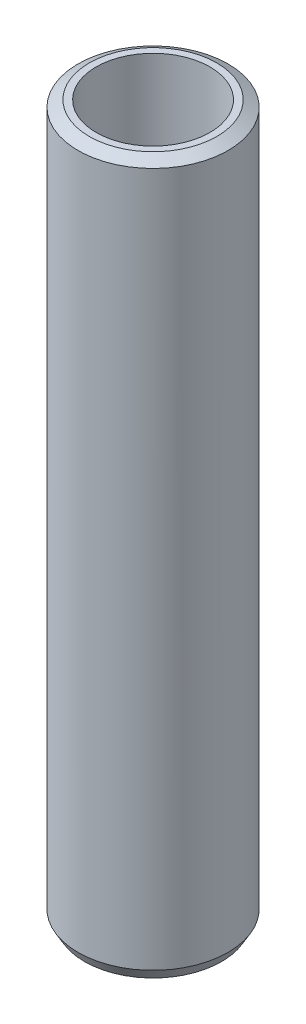
SolidWorks part; units mm, degrees
ref_plane "Front Plane" through (0, 0, 0) normal (0, 0, 1) x (1, 0, 0)
ref_plane "Top Plane" through (0, 0, 0) normal (0, 1, 0) x (1, 0, 0)
ref_plane "Right Plane" through (0, 0, 0) normal (1, 0, 0) x (0, 0, -1)
sketch "Sketch1" plane through (0, 0, 0) normal (0, 1, 0) x (1, 0, 0)
  circle A0 centre (0, 0) radius 50
  dimension "SHAFT_OD" = 100
extrude "Boss-Extrude1" add sketch "Sketch1" along normal blind 474.5336
sketch "Sketch2" plane through (0, 0, 0) normal (0, 1, 0) x (1, 0, 0)
  circle A0 centre (0, 0) radius 37.9012
  dimension "BORE_D" = 75.8024
extrude "Cut-Extrude1" cut sketch "Sketch2" along normal through all
chamfer "Chamfer1" distance 4.3375 angle 60 2 edges at (0, 474.5336, 50) (0, 0, 50) first distance on face at (0, 474.5336, 50) first distance on face at (0, 0, 37.9012)
